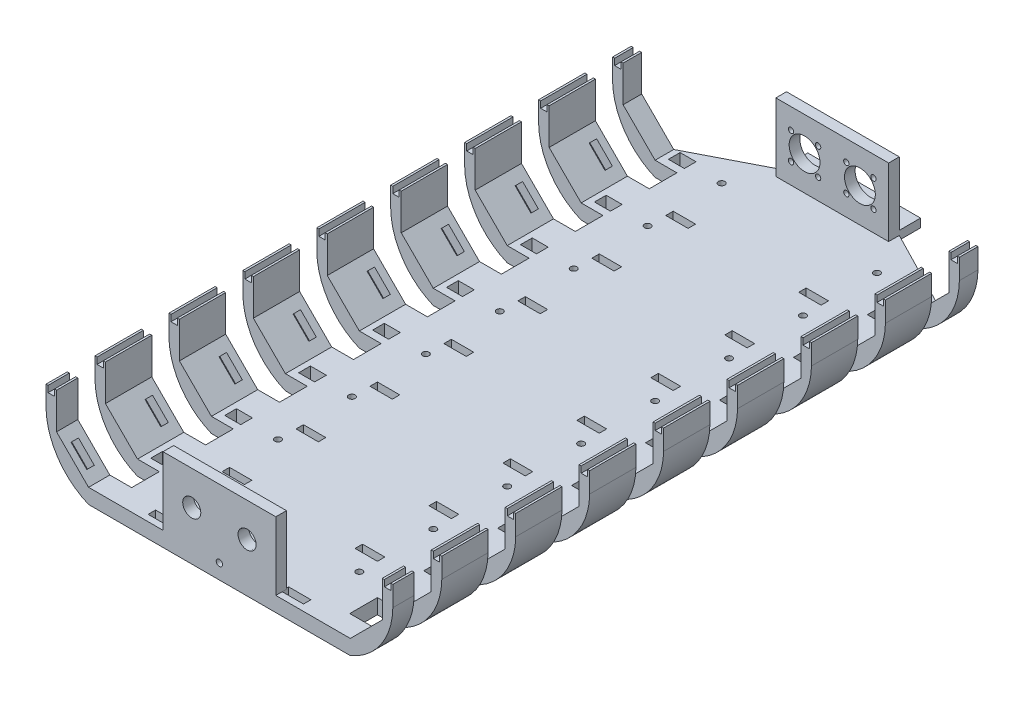
SolidWorks part; units mm, degrees
ref_plane "Front Plane" through (0, 0, 0) normal (0, 0, 1) x (1, 0, 0)
ref_plane "Top Plane" through (0, 0, 0) normal (0, 1, 0) x (1, 0, 0)
ref_plane "Right Plane" through (0, 0, 0) normal (1, 0, 0) x (0, 0, -1)
sketch "Sketch1" plane through (0, 0, 0) normal (0, 1, 0) x (1, 0, 0)
  line L0 (0, -135) -> (0, 135) construction
  line L1 (-13, 135) -> (-36, 135)
  line L2 (13, -135) -> (-13, -135)
  line L3 (13, -135) -> (13, 135) construction
  line L4 (13, 135) -> (-13, 135)
  line L5 (-13, -135) -> (-13, 135) construction
  line L8 (-36, 135) -> (-36, -135) construction
  line L9 (-36, -135) -> (-13, -135)
  line L10 (-36, 135) -> (-61.5, 135)
  line L11 (-61.5, 135) -> (-61.5, -135)
  line L12 (-61.5, -135) -> (-36, -135)
  line L13 (36, -135) -> (13, -135)
  line L14 (61.5, -135) -> (36, -135)
  line L15 (61.5, 135) -> (61.5, -135)
  line L16 (36, 135) -> (36, -135) construction
  line L17 (13, 135) -> (36, 135)
  line L18 (36, 135) -> (61.5, 135)
  point P0 (0, 0)
  point P4 (0, 0)
  dimension "D1" = 270
  dimension "D2" = 26
  dimension "D3" = 23
  dimension "D4" = 123
extrude "Boss-Extrude1" add sketch "Sketch1" along normal blind 7
sketch "Sketch2" plane through (0, 7, 0) normal (0, 1, 0) x (1, 0, 0)
  line L0 (61.5, -135) -> (61.5, 135) construction
  line L1 (-61.5, -135) -> (61.5, -135)
  line L2 (-61.5, -135) -> (-61.5, -130)
  line L3 (-61.5, -130) -> (61.5, -130)
  line L4 (61.5, -135) -> (61.5, -130)
  line L21 (-26.5, 130) -> (-26.5, -130) construction
  dimension "D1" = 5
extrude "Boss-Extrude2" add sketch "Sketch2" along normal blind 32
sketch "Sketch3" plane through (0, 0, 135) normal (0, 0, 1) x (1, 0, 0)
  line L0 (0, 39) -> (0, 0) construction
  line L2 (-61.5, 39) -> (-61.5, 7) construction
  line L3 (-61.5, 39) -> (61.5, 39) construction
  line L5 (-61.5, 39) -> (-61.5, 0) construction
  line L6 (-61.5, 23) -> (61.5, 23) construction
  line L7 (61.5, 39) -> (61.5, 0) construction
  circle A0 centre (-13, 23) radius 4.25
  circle A1 centre (13, 23) radius 4.25
  dimension "D1" = 8.5
  dimension "D2" = 8.5
  dimension "D3" = 26
  dimension "D4" = 13
  dimension "D5" = 32
  dimension "D6" = 16
sketch "Sketch9" plane through (0, 0, -135) normal (0, 0, -1) x (-1, 0, 0)
  line L1 (-61.5, 7) -> (61.5, 7)
  line L2 (-61.5, 7) -> (-61.5, 0)
  line L3 (-61.5, 0) -> (61.5, 0)
  line L4 (61.5, 7) -> (61.5, 0)
extrude "Boss-Extrude4" add sketch "Sketch9" along normal blind 5
sketch "Sketch13" plane through (0, 0, 135) normal (0, 0, 1) x (1, 0, 0)
  line L0 (-61.5, 39) -> (-61.5, 7)
  line L1 (-61.5, 39) -> (-61.5, 0) construction
  line L2 (-61.5, 39) -> (-26.5, 39)
  line L3 (-61.5, 39) -> (61.5, 39) construction
  line L4 (-26.5, 39) -> (-26.5, 7)
  line L5 (-26.5, 7) -> (-61.5, 7)
  line L6 (0, 39) -> (0, 5.5161) construction
  line L7 (26.5, 39) -> (26.5, 7)
  line L8 (61.5, 39) -> (26.5, 39)
  line L9 (61.5, 39) -> (61.5, 7)
  line L10 (26.5, 7) -> (61.5, 7)
  dimension "D1" = 32
  dimension "D2" = 35
extrude "Cut-Extrude5" cut sketch "Sketch13" against normal blind 11
sketch "Sketch14" plane through (0, 0, 135) normal (0, 0, 1) x (1, 0, 0)
  line L0 (0, 39) -> (0, 0) construction
  line L1 (-26.5, 39) -> (26.5, 39) construction
  line L2 (-81.5, 39) -> (0, 39) construction
  line L3 (-61.5, 0) -> (-81.5, 20) construction
  line L5 (-76.55, 22.05) -> (-61.5, 7)
  line L6 (-61.5, 0) -> (61.5, 0) construction
  line L7 (-61.5, 7) -> (-61.5, 0)
  line L12 (-81.5, 20) -> (-81.5, 39) construction
  line L13 (-81.5, 39) -> (-76.55, 39)
  line L14 (-76.55, 39) -> (-76.55, 22.05)
  line L21 (-61.5, 7) -> (-61.5, 39) construction
  line L22 (-81.5, 39) -> (-81.5, 29.5)
  line L23 (81.5, 39) -> (76.55, 39)
  line L24 (76.55, 39) -> (76.55, 22.05)
  line L25 (76.55, 22.05) -> (61.5, 7)
  line L26 (61.5, 7) -> (61.5, 0)
  line L27 (81.5, 39) -> (81.5, 29.5)
  arc A0 (-61.5, 0) -> (-81.5, 29.5) centre (-49.0062, 30) cw
  arc A1 (61.5, 0) -> (81.5, 29.5) centre (49.0062, 30) ccw
  dimension "D1" = 28.2843
  dimension "D2" = 45
  dimension "D3" = 4.95
  dimension "D4" = 20
  dimension "D5" = 4.9497
  dimension "D6" = 21.2839
  dimension "D7" = 30
  dimension "D8" = 9.5
extrude "Boss-Extrude10" add sketch "Sketch14" against normal blind 275
sketch "Sketch17" plane through (0, 7, 0) normal (0, 1, 0) x (1, 0, 0)
  line L0 (-26.5, 130) -> (26.5, 130) construction
  line L1 (0, 130) -> (0, 161) construction
  line L2 (-26.5, -135) -> (-26.5, 161) construction
  line L3 (26.5, -135) -> (26.5, 161) construction
  line L4 (26.5, 161) -> (-26.5, 161) construction
  line L5 (0, 161) -> (0, 226) construction
  line L6 (-61.5, 140) -> (-26.5, 226)
  line L7 (-26.5, 226) -> (0, 226)
  line L8 (0, 226) -> (26.5, 226)
  line L9 (26.5, 226) -> (61.5, 140)
  line L10 (26.5, 161) -> (26.5, 226) construction
  line L11 (-26.5, 161) -> (-26.5, 226) construction
  line L12 (-61.5, 140) -> (61.5, 140)
  line L13 (-61.5, 140) -> (61.5, 140) construction
  dimension "D1" = 31
  dimension "D2" = 296
  dimension "D3" = 90
  dimension "D4" = 65
  dimension "D5" = 10
extrude "Boss-Extrude13" add sketch "Sketch17" against normal blind 7 contours L12 L9 L8 L7 L6
sketch "Sketch18" plane through (0, 7, 0) normal (0, 1, 0) x (1, 0, 0)
  line L0 (-26.5, 127) -> (26.5, 127) construction
  line L1 (0, 127) -> (0, 158) construction
  line L2 (-26.5, 135) -> (-26.5, 158) construction
  line L3 (26.5, 132) -> (26.5, 158) construction
  line L4 (-26.5, 158) -> (-26.5, 153)
  line L5 (-26.5, 153) -> (26.5, 153)
  line L6 (26.5, 153) -> (26.5, 158)
  line L7 (26.5, 158) -> (-26.5, 158)
  line L8 (-61.5, 140) -> (-61.5, -135) construction
  line L9 (76.55, 140) -> (61.5, 140) construction
  dimension "D1" = 31
  dimension "D2" = 5
  dimension "D3" = 35
  dimension "D4" = 53
  dimension "D5" = 13
extrude "Boss-Extrude14" add sketch "Sketch18" along normal blind 32
extrude "Cut-Extrude8" cut sketch "Sketch3" against normal blind 334
sketch "Sketch19" plane through (0, 0, -153) normal (0, 0, 1) x (1, 0, 0)
  line L0 (0, 39) -> (0, 0) construction
  line L1 (-26.5, 39) -> (26.5, 39) construction
  line L3 (-6.636, 16.636) -> (-19.364, 16.636) construction
  line L4 (-6.636, 16.636) -> (-6.636, 29.364) construction
  line L5 (-6.636, 29.364) -> (-19.364, 29.364) construction
  line L6 (-19.364, 16.636) -> (-19.364, 29.364) construction
  line L7 (-6.636, 16.636) -> (-19.364, 29.364) construction
  line L8 (-6.636, 29.364) -> (-19.364, 16.636) construction
  circle A0 centre (-13, 23) radius 7.25
  circle A1 centre (-6.636, 16.636) radius 1.25
  circle A2 centre (-6.636, 29.364) radius 1.25
  circle A3 centre (-19.364, 29.364) radius 1.25
  circle A4 centre (-19.364, 16.636) radius 1.25
  circle A5 centre (13, 23) radius 7.25
  circle A6 centre (19.364, 16.636) radius 1.25
  circle A7 centre (6.636, 16.636) radius 1.25
  circle A8 centre (6.636, 29.364) radius 1.25
  circle A9 centre (19.364, 29.364) radius 1.25
  dimension "D1" = 14.5
  dimension "D4" = 2.5
  dimension "D5" = 2.5
  dimension "D6" = 2.5
  dimension "D7" = 2.5
  dimension "D2" = 18
  dimension "D3" = 18
  dimension "D8" = 12.7279
extrude "Cut-Extrude9" cut sketch "Sketch19" against normal blind 334
sketch "Sketch29" plane through (0, 7, 0) normal (0, 1, 0) x (1, 0, 0)
  line L0 (-61.5, 140) -> (-26.5, 158)
  line L1 (-26.5, 158) -> (26.5, 158)
  line L2 (26.5, 158) -> (61.5, 140)
  line L3 (61.5, 140) -> (26.5, 226)
  line L4 (26.5, 226) -> (-26.5, 226)
  line L5 (-26.5, 226) -> (-61.5, 140)
extrude "Cut-Extrude13" cut sketch "Sketch29" against normal blind 19
sketch "Sketch32" plane through (0, 7, 0) normal (0, 1, 0) x (1, 0, 0)
  line L0 (-61.5, 137.5) -> (-55, 137.5) construction
  line L1 (-61.5, 140) -> (-26.5, 140) construction
  line L3 (-61.5, 140) -> (-61.5, 130) construction
  line L4 (0, 158) -> (0, -135) construction
  line L5 (26.5, 158) -> (-26.5, 158) construction
  line L6 (-26.5, -135) -> (26.5, -135) construction
  line L7 (-61.5, 130) -> (-26.5, 130) construction
  line L8 (-81.5, 131.25) -> (-51.25, 131.25)
  line L9 (-26.5, 140) -> (-26.5, 130) construction
  line L10 (-81.5, 131.25) -> (-81.5, 118.25)
  line L11 (-51.25, 134.75) -> (-58.75, 134.75)
  line L12 (-51.25, 134.75) -> (-51.25, 140.25)
  line L13 (-51.25, 140.25) -> (-58.75, 140.25)
  line L14 (-58.75, 134.75) -> (-58.75, 140.25)
  line L15 (-51.25, 134.75) -> (-58.75, 140.25) construction
  line L16 (-51.25, 140.25) -> (-58.75, 134.75) construction
  line L23 (-81.5, 118.25) -> (-51.25, 118.25)
  line L24 (-51.25, 131.25) -> (-51.25, 118.25)
  line L25 (-81.5, 96.5) -> (-81.5, 83.5)
  line L26 (-81.5, 96.5) -> (-51.25, 96.5)
  line L27 (-51.25, 96.5) -> (-51.25, 83.5)
  line L28 (-81.5, 83.5) -> (-51.25, 83.5)
  line L29 (-51.25, 100) -> (-51.25, 105.5)
  line L30 (-51.25, 100) -> (-58.75, 100)
  line L31 (-58.75, 100) -> (-58.75, 105.5)
  line L32 (-51.25, 105.5) -> (-58.75, 105.5)
  line L37 (-81.5, 61.75) -> (-81.5, 48.75)
  line L38 (-81.5, 61.75) -> (-51.25, 61.75)
  line L39 (-51.25, 61.75) -> (-51.25, 48.75)
  line L40 (-81.5, 48.75) -> (-51.25, 48.75)
  line L41 (-51.25, 65.25) -> (-51.25, 70.75)
  line L42 (-51.25, 65.25) -> (-58.75, 65.25)
  line L43 (-58.75, 65.25) -> (-58.75, 70.75)
  line L44 (-51.25, 70.75) -> (-58.75, 70.75)
  line L49 (-81.5, 27) -> (-81.5, 14)
  line L50 (-81.5, 27) -> (-51.25, 27)
  line L51 (-51.25, 27) -> (-51.25, 14)
  line L52 (-81.5, 14) -> (-51.25, 14)
  line L53 (-51.25, 30.5) -> (-51.25, 36)
  line L54 (-51.25, 30.5) -> (-58.75, 30.5)
  line L55 (-58.75, 30.5) -> (-58.75, 36)
  line L56 (-51.25, 36) -> (-58.75, 36)
  line L61 (-81.5, -7.75) -> (-81.5, -20.75)
  line L62 (-81.5, -7.75) -> (-51.25, -7.75)
  line L63 (-51.25, -7.75) -> (-51.25, -20.75)
  line L64 (-81.5, -20.75) -> (-51.25, -20.75)
  line L65 (-51.25, -4.25) -> (-51.25, 1.25)
  line L66 (-51.25, -4.25) -> (-58.75, -4.25)
  line L67 (-58.75, -4.25) -> (-58.75, 1.25)
  line L68 (-51.25, 1.25) -> (-58.75, 1.25)
  line L73 (-81.5, -42.5) -> (-81.5, -55.5)
  line L74 (-81.5, -42.5) -> (-51.25, -42.5)
  line L75 (-51.25, -42.5) -> (-51.25, -55.5)
  line L76 (-81.5, -55.5) -> (-51.25, -55.5)
  line L77 (-51.25, -39) -> (-51.25, -33.5)
  line L78 (-51.25, -39) -> (-58.75, -39)
  line L79 (-58.75, -39) -> (-58.75, -33.5)
  line L80 (-51.25, -33.5) -> (-58.75, -33.5)
  line L85 (-81.5, -77.25) -> (-81.5, -90.25)
  line L86 (-81.5, -77.25) -> (-51.25, -77.25)
  line L87 (-51.25, -77.25) -> (-51.25, -90.25)
  line L88 (-81.5, -90.25) -> (-51.25, -90.25)
  line L89 (-51.25, -73.75) -> (-51.25, -68.25)
  line L90 (-51.25, -73.75) -> (-58.75, -73.75)
  line L91 (-58.75, -73.75) -> (-58.75, -68.25)
  line L92 (-51.25, -68.25) -> (-58.75, -68.25)
  line L97 (-81.5, -112) -> (-81.5, -125)
  line L98 (-81.5, -112) -> (-51.25, -112)
  line L99 (-51.25, -112) -> (-51.25, -125)
  line L100 (-81.5, -125) -> (-51.25, -125)
  line L101 (-51.25, -108.5) -> (-51.25, -103)
  line L102 (-51.25, -108.5) -> (-58.75, -108.5)
  line L103 (-58.75, -108.5) -> (-58.75, -103)
  line L104 (-51.25, -103) -> (-58.75, -103)
  line L109 (-26.5, -130) -> (-26.5, -125) construction
  line L110 (-26.5, -125) -> (-51.25, -125) construction
  line L111 (26.5, -125) -> (51.25, -125) construction
  line L112 (26.5, -130) -> (26.5, -125) construction
  line L115 (51.25, 140.25) -> (58.75, 134.75) construction
  line L116 (51.25, 134.75) -> (58.75, 140.25) construction
  line L117 (26.5, 140) -> (26.5, 130) construction
  line L118 (61.5, 130) -> (26.5, 130) construction
  line L119 (61.5, 140) -> (61.5, 130) construction
  line L120 (61.5, 140) -> (26.5, 140) construction
  line L121 (61.5, 137.5) -> (55, 137.5) construction
  line L126 (51.25, -103) -> (58.75, -103)
  line L127 (58.75, -108.5) -> (58.75, -103)
  line L128 (51.25, -108.5) -> (58.75, -108.5)
  line L129 (51.25, -108.5) -> (51.25, -103)
  line L130 (81.5, -125) -> (51.25, -125)
  line L131 (51.25, -112) -> (51.25, -125)
  line L132 (81.5, -112) -> (51.25, -112)
  line L133 (81.5, -112) -> (81.5, -125)
  line L138 (51.25, -68.25) -> (58.75, -68.25)
  line L139 (58.75, -73.75) -> (58.75, -68.25)
  line L140 (51.25, -73.75) -> (58.75, -73.75)
  line L141 (51.25, -73.75) -> (51.25, -68.25)
  line L142 (81.5, -90.25) -> (51.25, -90.25)
  line L143 (51.25, -77.25) -> (51.25, -90.25)
  line L144 (81.5, -77.25) -> (51.25, -77.25)
  line L145 (81.5, -77.25) -> (81.5, -90.25)
  line L150 (51.25, -33.5) -> (58.75, -33.5)
  line L151 (58.75, -39) -> (58.75, -33.5)
  line L152 (51.25, -39) -> (58.75, -39)
  line L153 (51.25, -39) -> (51.25, -33.5)
  line L154 (81.5, -55.5) -> (51.25, -55.5)
  line L155 (51.25, -42.5) -> (51.25, -55.5)
  line L156 (81.5, -42.5) -> (51.25, -42.5)
  line L157 (81.5, -42.5) -> (81.5, -55.5)
  line L162 (51.25, 1.25) -> (58.75, 1.25)
  line L163 (58.75, -4.25) -> (58.75, 1.25)
  line L164 (51.25, -4.25) -> (58.75, -4.25)
  line L165 (51.25, -4.25) -> (51.25, 1.25)
  line L166 (81.5, -20.75) -> (51.25, -20.75)
  line L167 (51.25, -7.75) -> (51.25, -20.75)
  line L168 (81.5, -7.75) -> (51.25, -7.75)
  line L169 (81.5, -7.75) -> (81.5, -20.75)
  line L174 (51.25, 36) -> (58.75, 36)
  line L175 (58.75, 30.5) -> (58.75, 36)
  line L176 (51.25, 30.5) -> (58.75, 30.5)
  line L177 (51.25, 30.5) -> (51.25, 36)
  line L178 (81.5, 14) -> (51.25, 14)
  line L179 (51.25, 27) -> (51.25, 14)
  line L180 (81.5, 27) -> (51.25, 27)
  line L181 (81.5, 27) -> (81.5, 14)
  line L186 (51.25, 70.75) -> (58.75, 70.75)
  line L187 (58.75, 65.25) -> (58.75, 70.75)
  line L188 (51.25, 65.25) -> (58.75, 65.25)
  line L189 (51.25, 65.25) -> (51.25, 70.75)
  line L190 (81.5, 48.75) -> (51.25, 48.75)
  line L191 (51.25, 61.75) -> (51.25, 48.75)
  line L192 (81.5, 61.75) -> (51.25, 61.75)
  line L193 (81.5, 61.75) -> (81.5, 48.75)
  line L198 (51.25, 105.5) -> (58.75, 105.5)
  line L199 (58.75, 100) -> (58.75, 105.5)
  line L200 (51.25, 100) -> (58.75, 100)
  line L201 (51.25, 100) -> (51.25, 105.5)
  line L202 (81.5, 83.5) -> (51.25, 83.5)
  line L203 (51.25, 96.5) -> (51.25, 83.5)
  line L204 (81.5, 96.5) -> (51.25, 96.5)
  line L205 (81.5, 96.5) -> (81.5, 83.5)
  line L206 (51.25, 131.25) -> (51.25, 118.25)
  line L207 (81.5, 118.25) -> (51.25, 118.25)
  line L212 (58.75, 134.75) -> (58.75, 140.25)
  line L213 (51.25, 140.25) -> (58.75, 140.25)
  line L214 (51.25, 134.75) -> (51.25, 140.25)
  line L215 (51.25, 134.75) -> (58.75, 134.75)
  line L216 (81.5, 131.25) -> (81.5, 118.25)
  line L217 (81.5, 131.25) -> (51.25, 131.25)
  line L218 (-81.5, 140) -> (-81.5, -135) construction
  circle A0 centre (-36.5, 137.5) radius 1.5
  circle A1 centre (-36.5, 102.75) radius 1.5
  circle A2 centre (-36.5, 68) radius 1.5
  circle A3 centre (-36.5, 33.25) radius 1.5
  circle A4 centre (-36.5, -1.5) radius 1.5
  circle A5 centre (-36.5, -36.25) radius 1.5
  circle A6 centre (-36.5, -71) radius 1.5
  circle A7 centre (-36.5, -105.75) radius 1.5
  circle A8 centre (36.5, -105.75) radius 1.5
  circle A9 centre (36.5, -71) radius 1.5
  circle A10 centre (36.5, -36.25) radius 1.5
  circle A11 centre (36.5, -1.5) radius 1.5
  circle A12 centre (36.5, 33.25) radius 1.5
  circle A13 centre (36.5, 68) radius 1.5
  circle A14 centre (36.5, 102.75) radius 1.5
  circle A15 centre (36.5, 137.5) radius 1.5
  point P21 (-55, 137.5)
  dimension "D7" = 3
  dimension "D1" = 10
  dimension "D2" = 35
  dimension "D3" = 5.5
  dimension "D4" = 7.5
  dimension "D5" = 2.75
  dimension "D6" = 2.5
  dimension "D8" = 25
  dimension "D9" = 2.5
  dimension "D10" = 3.5
  dimension "D15" = 13
  dimension "D17" = 5
  dimension "D16" = 8
extrude "Cut-Extrude16" cut sketch "Sketch32" against normal through all both and the other way through all
sketch "Sketch33" plane through (0, 7, 0) normal (0, 1, 0) x (1, 0, 0)
  line L0 (-61.5, 118.25) -> (-26, 118.25) construction
  line L1 (-26, 118.25) -> (-26, 114.75) construction
  line L2 (0, 158) -> (0, -135) construction
  line L3 (-26, 114.75) -> (-36.5, 114.75)
  line L4 (-26, 114.75) -> (-26, 111.25)
  line L5 (-26, 111.25) -> (-36.5, 111.25)
  line L6 (-36.5, 114.75) -> (-36.5, 111.25)
  line L7 (26.5, 158) -> (-26.5, 158) construction
  line L8 (-26.5, -135) -> (26.5, -135) construction
  line L9 (-26, 80) -> (-26, 76.5)
  line L10 (-26, 80) -> (-36.5, 80)
  line L11 (-36.5, 80) -> (-36.5, 76.5)
  line L12 (-26, 76.5) -> (-36.5, 76.5)
  line L13 (-26, 45.25) -> (-26, 41.75)
  line L14 (-26, 45.25) -> (-36.5, 45.25)
  line L15 (-36.5, 45.25) -> (-36.5, 41.75)
  line L16 (-26, 41.75) -> (-36.5, 41.75)
  line L17 (-26, 10.5) -> (-26, 7)
  line L18 (-26, 10.5) -> (-36.5, 10.5)
  line L19 (-36.5, 10.5) -> (-36.5, 7)
  line L20 (-26, 7) -> (-36.5, 7)
  line L21 (-26, -24.25) -> (-26, -27.75)
  line L22 (-26, -24.25) -> (-36.5, -24.25)
  line L23 (-36.5, -24.25) -> (-36.5, -27.75)
  line L24 (-26, -27.75) -> (-36.5, -27.75)
  line L25 (-26, -59) -> (-26, -62.5)
  line L26 (-26, -59) -> (-36.5, -59)
  line L27 (-36.5, -59) -> (-36.5, -62.5)
  line L28 (-26, -62.5) -> (-36.5, -62.5)
  line L29 (-26, -93.75) -> (-26, -97.25)
  line L30 (-26, -93.75) -> (-36.5, -93.75)
  line L31 (-36.5, -93.75) -> (-36.5, -97.25)
  line L32 (-26, -97.25) -> (-36.5, -97.25)
  line L33 (-26, -128.5) -> (-26, -132)
  line L34 (-26, -128.5) -> (-36.5, -128.5)
  line L35 (-36.5, -128.5) -> (-36.5, -132)
  line L36 (-26, -132) -> (-36.5, -132)
  line L37 (-51.25, -125) -> (-51.25, -128.5) construction
  line L38 (-51.25, -128.5) -> (-16.25, -128.5) construction
  line L39 (26, -128.5) -> (36.5, -128.5)
  line L40 (36.5, -128.5) -> (36.5, -132)
  line L41 (26, -132) -> (36.5, -132)
  line L42 (26, -128.5) -> (26, -132)
  line L43 (26, -93.75) -> (36.5, -93.75)
  line L44 (36.5, -93.75) -> (36.5, -97.25)
  line L45 (26, -97.25) -> (36.5, -97.25)
  line L46 (26, -93.75) -> (26, -97.25)
  line L47 (26, -59) -> (36.5, -59)
  line L48 (36.5, -59) -> (36.5, -62.5)
  line L49 (26, -62.5) -> (36.5, -62.5)
  line L50 (26, -59) -> (26, -62.5)
  line L51 (26, -24.25) -> (36.5, -24.25)
  line L52 (36.5, -24.25) -> (36.5, -27.75)
  line L53 (26, -27.75) -> (36.5, -27.75)
  line L54 (26, -24.25) -> (26, -27.75)
  line L55 (26, 10.5) -> (36.5, 10.5)
  line L56 (36.5, 10.5) -> (36.5, 7)
  line L57 (26, 7) -> (36.5, 7)
  line L58 (26, 10.5) -> (26, 7)
  line L59 (26, 45.25) -> (36.5, 45.25)
  line L60 (36.5, 45.25) -> (36.5, 41.75)
  line L61 (26, 41.75) -> (36.5, 41.75)
  line L62 (26, 45.25) -> (26, 41.75)
  line L63 (26, 80) -> (36.5, 80)
  line L64 (36.5, 80) -> (36.5, 76.5)
  line L65 (26, 76.5) -> (36.5, 76.5)
  line L66 (26, 80) -> (26, 76.5)
  line L67 (26, 111.25) -> (36.5, 111.25)
  line L68 (36.5, 114.75) -> (36.5, 111.25)
  line L69 (26, 114.75) -> (36.5, 114.75)
  line L70 (26, 114.75) -> (26, 111.25)
  dimension "D1" = 35.5
  dimension "D2" = 3.5
  dimension "D3" = 3.5
  dimension "D4" = 10.5
  dimension "D6" = 3.5
  dimension "D7" = 35
  dimension "D5" = 8
extrude "Cut-Extrude18" cut sketch "Sketch33" against normal blind 4.5
sketch "Sketch34" plane through (27.25, -27.25, 0) normal (-0.7071, 0.7071, 0) x (0, 0, 1)
  line L0 (-118.25, 59.0788) -> (-96.5, 59.0788) construction
  line L1 (-118.25, 48.4368) -> (-118.25, 69.7207) construction
  line L2 (-96.5, 69.7207) -> (-96.5, 48.4368) construction
  line L3 (-113.25, 69.7207) -> (-113.25, 48.4368) construction
  line L4 (-118.25, 69.7207) -> (-96.5, 69.7207) construction
  line L5 (-96.5, 48.4368) -> (-118.25, 48.4368) construction
  line L6 (-76.7143, 53.8288) -> (-76.7143, 64.3288)
  line L7 (-111.5, 53.8288) -> (-115, 53.8288)
  line L8 (-111.5, 53.8288) -> (-111.5, 64.3288)
  line L9 (-111.5, 64.3288) -> (-115, 64.3288)
  line L10 (-115, 53.8288) -> (-115, 64.3288)
  line L11 (-111.5, 53.8288) -> (-115, 64.3288) construction
  line L12 (-111.5, 64.3288) -> (-115, 53.8288) construction
  line L13 (-76.7143, 53.8288) -> (-80.2143, 53.8288)
  line L14 (-80.2143, 53.8288) -> (-80.2143, 64.3288)
  line L15 (-76.7143, 64.3288) -> (-80.2143, 64.3288)
  line L16 (-41.9286, 53.8288) -> (-41.9286, 64.3288)
  line L17 (-41.9286, 53.8288) -> (-45.4286, 53.8288)
  line L18 (-45.4286, 53.8288) -> (-45.4286, 64.3288)
  line L19 (-41.9286, 64.3288) -> (-45.4286, 64.3288)
  line L20 (-7.1429, 53.8288) -> (-7.1429, 64.3288)
  line L21 (-7.1429, 53.8288) -> (-10.6429, 53.8288)
  line L22 (-10.6429, 53.8288) -> (-10.6429, 64.3288)
  line L23 (-7.1429, 64.3288) -> (-10.6429, 64.3288)
  line L24 (27.6429, 53.8288) -> (27.6429, 64.3288)
  line L25 (27.6429, 53.8288) -> (24.1429, 53.8288)
  line L26 (24.1429, 53.8288) -> (24.1429, 64.3288)
  line L27 (27.6429, 64.3288) -> (24.1429, 64.3288)
  line L28 (62.4286, 53.8288) -> (62.4286, 64.3288)
  line L29 (62.4286, 53.8288) -> (58.9286, 53.8288)
  line L30 (58.9286, 53.8288) -> (58.9286, 64.3288)
  line L31 (62.4286, 64.3288) -> (58.9286, 64.3288)
  line L32 (97.2143, 53.8288) -> (97.2143, 64.3288)
  line L33 (97.2143, 53.8288) -> (93.7143, 53.8288)
  line L34 (93.7143, 53.8288) -> (93.7143, 64.3288)
  line L35 (97.2143, 64.3288) -> (93.7143, 64.3288)
  line L36 (132, 53.8288) -> (132, 64.3288)
  line L37 (132, 53.8288) -> (128.5, 53.8288)
  line L38 (128.5, 53.8288) -> (128.5, 64.3288)
  line L39 (132, 64.3288) -> (128.5, 64.3288)
  line L40 (125, 59.0788) -> (135, 59.0788) construction
  line L41 (125, 48.4368) -> (125, 69.7207) construction
  line L42 (135, 69.7207) -> (135, 48.4368) construction
  line L43 (128.5, 48.4368) -> (128.5, 69.7207) construction
  line L44 (135, 48.4368) -> (125, 48.4368) construction
  line L45 (125, 69.7207) -> (135, 69.7207) construction
  point P12 (-113.25, 59.0788)
  dimension "D1" = 5
  dimension "D2" = 3.5
  dimension "D3" = 10.5
  dimension "D5" = 3.5
  dimension "D4" = 8
extrude "Cut-Extrude19" cut sketch "Sketch34" against normal blind 4.5
mirror "Mirror1" about plane through (0, 0, 0) normal (1, 0, 0) of "Cut-Extrude19"
sketch "Sketch35" plane through (0, 39, 0) normal (0, 1, 0) x (1, 0, 0)
  line L0 (-79.025, 140) -> (-79.025, -135) construction
  line L1 (-76.55, 140) -> (-81.5, 140) construction
  line L2 (-76.55, -135) -> (-81.5, -135) construction
  line L3 (-80.525, -135) -> (-77.525, -135)
  line L4 (-80.525, -135) -> (-80.525, 140)
  line L5 (-80.525, 140) -> (-77.525, 140)
  line L6 (-77.525, 140) -> (-77.525, -135)
  line L7 (0, -135) -> (0, 158) construction
  line L8 (-26.5, -135) -> (26.5, -135) construction
  line L9 (26.5, 158) -> (-26.5, 158) construction
  line L10 (80.525, 140) -> (77.525, 140)
  line L11 (80.525, -135) -> (80.525, 140)
  line L12 (80.525, -135) -> (77.525, -135)
  line L13 (77.525, 140) -> (77.525, -135)
  point P8 (-79.025, -135)
  dimension "D1" = 1.5
extrude "Cut-Extrude20" cut sketch "Sketch35" against normal blind 3
sketch "Sketch36" plane through (0, 0, -158) normal (0, 0, -1) x (-1, 0, 0)
  line L5 (-26.5, 39) -> (-26.5, 7) construction
  line L6 (-26.5, 9.0853) -> (26.5, 9.0853)
  line L7 (-26.5, 9.0853) -> (-26.5, 5.0853)
  line L8 (-26.5, 5.0853) -> (26.5, 5.0853)
  line L9 (26.5, 9.0853) -> (26.5, 5.0853)
  line L10 (26.5, 0) -> (26.5, 7) construction
  line L11 (-26.5, 5.0853) -> (26.5, 5.0853) construction
  dimension "D1" = 4
extrude "Boss-Extrude15" add sketch "Sketch36" along normal blind 10
sketch "Sketch37" plane through (0, 0, 135) normal (0, 0, 1) x (1, 0, 0)
  line L0 (-26.5, 7) -> (26.5, 7) construction
  circle A0 centre (0, 7) radius 1.5
  dimension "D1" = 3
extrude "Cut-Extrude21" cut sketch "Sketch37" against normal blind 10 contours A0
draft "Draft1" type of draft neutral plane draft angle 1 faces to draft 2 face at (17.25, 23, 135) face at (-8.75, 23, 135) neutral plane through (61.5, 7, 135) neutral plane normal (0, 0, 1) parameters "D1"=1
